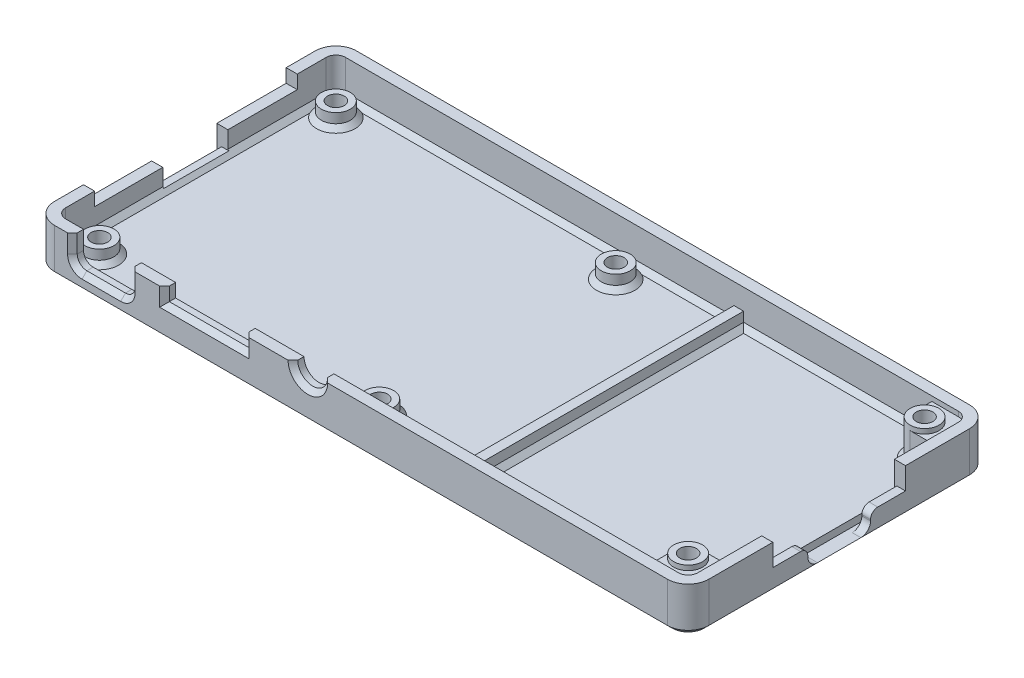
SolidWorks part; units mm, degrees
ref_plane "Front Plane" through (0, 0, 0) normal (0, 0, 1) x (1, 0, 0)
ref_plane "Top Plane" through (0, 0, 0) normal (0, 1, 0) x (1, 0, 0)
ref_plane "Right Plane" through (0, 0, 0) normal (1, 0, 0) x (0, 0, -1)
sketch "Sketch1" plane through (0, 0, 0) normal (0, 1, 0) x (1, 0, 0)
  line L0 (-71.5618, 3.106) -> (57.4382, 3.106) construction
  line L1 (-71.5618, 31.106) -> (57.4382, 31.106)
  line L2 (-71.5618, 31.106) -> (-71.5618, -24.894)
  line L3 (-71.5618, -24.894) -> (57.4382, -24.894)
  line L4 (57.4382, 31.106) -> (57.4382, -24.894)
  line L5 (-60.6618, -24.894) -> (-60.6618, -31.6828) construction
  line L6 (-68.0618, 27.606) -> (-10.0618, 27.606)
  line L7 (-68.0618, 27.606) -> (-68.0618, -21.394)
  line L8 (-68.0618, -21.394) -> (-10.0618, -21.394)
  line L9 (-10.0618, 27.606) -> (-10.0618, -21.394)
  line L10 (-39.5618, -24.894) -> (-39.5618, -31.6828) construction
  line L11 (-18.0618, -24.894) -> (-18.0618, -31.6828) construction
  line L12 (-65.4118, -26.5648) -> (-55.9118, -26.5648) construction
  line L13 (-48.0618, -26.5648) -> (-31.0618, -26.5648) construction
  line L14 (-22.0618, -26.5648) -> (-14.0618, -26.5648) construction
  line L15 (-72.5618, 9.606) -> (-72.5618, -3.394) construction
  line L16 (-71.5618, 3.106) -> (-72.5618, 3.106) construction
  dimension "D1" = 129
  dimension "D2" = 56
  dimension "D3" = 49
  dimension "D4" = 58
  dimension "D5" = 3.5
  dimension "D6" = 3.5
  dimension "D7" = 10.9
  dimension "D8" = 32
  dimension "D9" = 53.5
  dimension "D10" = 2
  dimension "D11" = 13
  dimension "D12" = 9.5
  dimension "D13" = 17
  dimension "D14" = 8
sketch "Sketch3" plane through (0, 0, 0) normal (0, 1, 0) x (1, 0, 0)
  line L4 (60.7382, 34.406) -> (-74.8618, 34.406)
  line L5 (-74.8618, 34.406) -> (-74.8618, -28.194)
  line L6 (-74.8618, -28.194) -> (60.7382, -28.194)
  line L7 (60.7382, -28.194) -> (60.7382, 34.406)
  line L8 (58.4382, 32.106) -> (-72.5618, 32.106)
  line L9 (58.4382, -25.894) -> (58.4382, 32.106)
  line L10 (-72.5618, -25.894) -> (58.4382, -25.894)
  line L11 (-72.5618, 32.106) -> (-72.5618, -25.894)
  line L12 (58.4382, 32.106) -> (-72.5618, 32.106)
  line L13 (58.4382, -25.894) -> (58.4382, 32.106)
  line L14 (-72.5618, -25.894) -> (58.4382, -25.894)
  line L15 (-72.5618, 32.106) -> (-72.5618, -25.894)
  line L16 (-7.0618, 3.106) -> (-7.0618, 34.406) construction
  line L17 (-71.5618, 3.106) -> (57.4382, 3.106) construction
  line L20 (-74.8618, 3.106) -> (52.7382, 3.106) construction
  line L25 (60.7382, -28.194) -> (60.7382, 34.406) construction
  line L26 (58.4382, -25.894) -> (58.4382, 32.106) construction
  dimension "D1" = 1
  dimension "D2" = 2.3
extrude "Boss-Extrude1" add sketch "Sketch3" along normal blind 9.3
sketch "Sketch5" plane through (0, 0, 0) normal (0, 1, 0) x (1, 0, 0)
  line L1 (-72.5618, 32.106) -> (58.4382, 32.106)
  line L2 (-72.5618, 32.106) -> (-72.5618, -25.894)
  line L3 (-72.5618, -25.894) -> (58.4382, -25.894)
  line L4 (58.4382, 32.106) -> (58.4382, -25.894)
extrude "Boss-Extrude2" add sketch "Sketch5" along normal blind 2
sketch "Sketch6" plane through (0, 2, 0) normal (0, 1, 0) x (1, 0, 0)
  circle A0 centre (-68.0618, 27.606) radius 3
  circle A1 centre (-68.0618, -21.394) radius 3
  circle A2 centre (-10.0618, -21.394) radius 3
  circle A3 centre (-10.0618, 27.606) radius 3
extrude "Boss-Extrude3" add sketch "Sketch6" along normal offset from surface (3 mm away) 4.3 up to face at (-7.0618, 9.3, -3.106)
sketch "Sketch10" plane through (0, 2, 0) normal (0, 1, 0) x (1, 0, 0)
  line L0 (58.4382, 32.106) -> (-72.5618, 32.106) construction
  line L1 (9.9382, 32.106) -> (11.9382, 32.106)
  line L2 (9.9382, 32.106) -> (9.9382, -25.894)
  line L3 (9.9382, -25.894) -> (11.9382, -25.894)
  line L4 (11.9382, 32.106) -> (11.9382, -25.894)
  line L5 (-72.5618, -25.894) -> (58.4382, -25.894) construction
  line L6 (-10.0618, 27.606) -> (-10.0618, -21.394) construction
  dimension "D1" = 2
  dimension "D2" = 20
extrude "Boss-Extrude4" add sketch "Sketch10" along normal offset from surface (3 mm away) 4.3 up to face at (-7.0618, 9.3, -3.106)
sketch "Sketch11" plane through (0, 0, 28.194) normal (0, 0, 1) x (1, 0, 0)
  line L0 (-74.8618, 9.3) -> (-74.8618, 0) construction
  line L1 (-66.8618, 9.3) -> (-54.8618, 9.3)
  line L2 (-66.8618, 9.3) -> (-66.8618, 3.5)
  line L3 (-66.8618, 3.5) -> (-54.8618, 3.5)
  line L4 (-54.8618, 9.3) -> (-54.8618, 3.5)
  line L6 (-60.8618, 9.3) -> (-60.6618, 0) construction
  line L7 (-65.4118, 0) -> (-55.9118, 0) construction
  line L9 (-47.778, 9.3) -> (-31.278, 9.3)
  line L10 (-47.778, 9.3) -> (-47.778, 6.5)
  line L11 (-47.778, 6.5) -> (-31.278, 6.5)
  line L12 (-31.278, 9.3) -> (-31.278, 6.5)
  line L14 (-39.5618, 0) -> (-39.528, 9.3) construction
  line L15 (-48.0618, 0) -> (-31.0618, 0) construction
  line L16 (-18.0618, 0) -> (-18.0618, 9.3) construction
  line L17 (-22.0618, 0) -> (-14.0618, 0) construction
  line L18 (-74.8618, 9.3) -> (60.7382, 9.3) construction
  circle A0 centre (-18.0618, 9.3) radius 3.1
  dimension "D5" = 6.2
  dimension "D1" = 0
  dimension "D2" = 12
  dimension "D3" = 0
  dimension "D4" = 16.5
  dimension "D6" = 8
  dimension "D7" = 5.8
  dimension "D8" = 2.8
extrude "Cut-Extrude1" cut sketch "Sketch11" against normal up to next
sketch "Sketch12" plane through (-74.8618, 0, 0) normal (-1, 0, 0) x (0, 0, 1)
  line L0 (-3.106, 0) -> (-3.106, 9.3) construction
  line L1 (-27.606, 0) -> (21.394, 0) construction
  line L2 (-34.406, 9.3) -> (28.194, 9.3) construction
  line L3 (-24.106, 6.5) -> (17.894, 6.5)
  line L4 (-9.7329, 6.5) -> (3.7671, 6.5)
  line L5 (-9.7329, 6.5) -> (-9.7329, 2.8)
  line L6 (-9.7329, 2.8) -> (3.7671, 2.8)
  line L7 (3.7671, 6.5) -> (3.7671, 2.8)
  line L8 (-24.106, 9.3) -> (17.894, 9.3)
  line L9 (-24.106, 9.3) -> (-24.106, 6.5)
  line L11 (17.894, 9.3) -> (17.894, 6.5)
  line L12 (-9.7329, 4.65) -> (3.7671, 4.65) construction
  point P17 (-3.106, 6.5)
  dimension "D1" = 13.5
  dimension "D2" = 2.8
  dimension "D3" = 3.7
  dimension "D4" = 6.5
extrude "Cut-Extrude2" cut sketch "Sketch12" against normal up to next contours L9 L3 L11 L8 | L7 L6 L5 L4
fillet "Fillet6" radius 2 1 edges at (58.4382, 5.65, -32.106)
fillet "Fillet8" radius 2 2 edges at (-72.5618, 5.65, 25.894) (-72.5618, 5.65, -32.106)
chamfer "Chamfer1" distance 1 angle 45 4 edges at (-68.0618, 2, 24.394) (-10.0618, 2, 24.394) (-10.0618, 2, -24.606) (-68.0618, 2, -24.606)
sketch "Sketch24" plane through (0, 2, 0) normal (0, 1, 0) x (1, 0, 0)
  line L0 (11.9382, 3.106) -> (61.5789, 3.106) construction
  line L1 (11.9382, -25.894) -> (11.9382, 32.106) construction
  line L2 (53.9382, -18.394) -> (58.4382, -18.394)
  line L3 (58.4382, -25.894) -> (58.4382, 30.106) construction
  line L4 (-68.0618, 27.606) -> (-10.0618, 27.606) construction
  line L5 (-68.0618, 27.606) -> (-68.0618, -21.394) construction
  line L6 (-68.0618, -21.394) -> (-10.0618, -21.394) construction
  line L7 (-10.0618, 27.606) -> (-10.0618, -21.394) construction
  line L8 (-10.0618, 27.606) -> (53.9382, 27.606) construction
  line L9 (-10.0618, 27.606) -> (-10.0618, -21.394) construction
  line L10 (-10.0618, -21.394) -> (53.9382, -21.394) construction
  line L11 (53.9382, 27.606) -> (53.9382, -21.394) construction
  line L12 (50.9382, -21.394) -> (50.9382, -25.894)
  line L13 (11.9382, -25.894) -> (58.4382, -25.894) construction
  line L14 (58.4382, -25.894) -> (58.4382, 30.106) construction
  line L15 (58.4382, -18.394) -> (58.4382, -25.894)
  line L16 (58.4382, -25.894) -> (50.9382, -25.894)
  line L17 (50.9382, 27.606) -> (50.9382, 32.106)
  line L18 (56.4382, 32.106) -> (-70.5618, 32.106) construction
  line L19 (53.9382, 24.606) -> (58.4382, 24.606)
  line L20 (58.4382, 24.606) -> (58.4382, 32.106)
  line L21 (58.4382, 32.106) -> (50.9382, 32.106)
  arc A0 (50.9382, -21.394) -> (53.9382, -18.394) centre (53.9382, -21.394) cw
  arc A1 (50.9382, 27.606) -> (53.9382, 24.606) centre (53.9382, 27.606) ccw
  dimension "D2" = 4.5
extrude "Boss-Extrude7" add sketch "Sketch24" along normal up to surface (7.3 mm away) up to face at (-8.3784, 9.3, -11.175)
fillet "Fillet20" radius 4.3 4 edges at (60.7382, 4.65, 28.194) (-74.8618, 4.65, -34.406) (-74.8618, 4.65, 28.194) (60.7382, 4.65, -34.406)
chamfer "Chamfer5" distance 1 angle 45 16 edges at (-71.976, 2, 25.3082) (-71.976, 2, -31.5202) (-30.3118, 2, 25.894) (-30.3118, 2, -32.106) (9.9382, 2, -3.106) (11.9382, 2, -3.106) (31.4382, 2, -32.106) (31.4382, 2, 25.894) (51.8169, 2, 19.2727) (58.4382, 2, -3.106) (51.8169, 2, -25.4847) (-72.5618, 2, -3.106) (50.9382, 2, -29.856) (56.1882, 2, -24.606) (56.1882, 2, 18.394) (50.9382, 2, 23.644)
hole_wizard "CSK for #4 Flat Head Socket Cap Screw1" positions "Sketch28" profile "Sketch27" countersink size "#4" standard "ANSI Inch"
sketch "Sketch28" plane through (0, 0, 0) normal (0, -1, 0) x (-1, 0, 0)
  point P0 (68.0618, 27.606)
  point P4 (68.0618, -21.394)
  point P8 (-53.9382, 27.606)
  point P12 (-53.9382, -21.394)
  point P15 (10.0618, -21.394)
  point P19 (10.0618, 27.606)
sketch "Sketch27" plane through (-68.0618, 0, -27.606) normal (1, 0, 0) x (0, 0, -1)
  line L0 (0, 0) -> (0, 15.0378)
  line L1 (0, 15.0378) -> (1.7272, 14)
  line L2 (1.7272, 14) -> (1.7272, 1.8805)
  line L3 (1.7272, 1.8805) -> (3.3619, 0)
  line L5 (3.3619, 0) -> (0, 0)
  line L6 (-1.7272, 1.8805) -> (-3.3619, 0) construction
  line L10 (0, 15.0378) -> (-1.7272, 14) construction
  line L11 (0, -6.35) -> (0, 107.95) construction
  dimension "Hole Dia." = 3.4544
  dimension "Hole Depth" = 14
  dimension "Near C'Sink Dia." = 6.7238
  dimension "Near C'Sink Angle" = 82
  dimension "Drill Angle" = 118
chamfer "Chamfer7" distance 1 angle 45 8 edges at (-74.8618, 0, -3.106) (-73.6023, 0, 26.9346) (-73.6023, 0, -33.1466) (-7.0618, 0, 28.194) (-7.0618, 0, -34.406) (59.4788, 0, 26.9346) (59.4788, 0, -33.1466) (60.7382, 0, -3.106)
chamfer "Chamfer8" distance 1 angle 45 1 edges at (-74.8618, 2.8, -2.9829)
sketch "Sketch29" plane through (0, 9.3, 0) normal (0, 1, 0) x (1, 0, 0)
  line L0 (53.9382, 24.606) -> (58.4382, 24.606)
  line L1 (58.4382, 24.606) -> (58.4382, 30.106)
  line L2 (56.4382, 32.106) -> (50.9382, 32.106)
  line L3 (50.9382, 32.106) -> (50.9382, 27.606)
  line L4 (53.9382, -18.394) -> (58.4382, -18.394)
  line L5 (58.4382, -18.394) -> (58.4382, -23.894)
  line L6 (56.4382, -25.894) -> (50.9382, -25.894)
  line L7 (50.9382, -25.894) -> (50.9382, -21.394)
  arc A0 (53.9382, 24.606) -> (50.9382, 27.606) centre (53.9382, 27.606) ccw
  arc A1 (56.4382, 32.106) -> (58.4382, 30.106) centre (56.4382, 30.106) cw
  arc A2 (50.9382, -21.394) -> (53.9382, -18.394) centre (53.9382, -21.394) ccw
  arc A3 (56.4382, -25.894) -> (58.4382, -23.894) centre (56.4382, -23.894) ccw
extrude "Cut-Extrude3" cut sketch "Sketch29" against normal blind 1
fillet "Fillet21" radius 2 2 edges at (-54.8618, 3.5, 27.044) (-66.8618, 3.5, 27.044)
chamfer "Chamfer9" distance 1 angle 45 9 edges at (-18.0618, 6.2, 28.194) (-31.278, 7.9, 28.194) (-39.528, 6.5, 28.194) (-47.778, 7.9, 28.194) (-54.8618, 7.4, 28.194) (-55.4476, 4.0858, 28.194) (-60.8618, 3.5, 28.194) (-66.276, 4.0858, 28.194) (-66.8618, 7.4, 28.194)
sketch "Sketch30" plane through (58.4382, 0, 0) normal (-1, 0, 0) x (0, 0, 1)
  line L1 (-16.856, 28.5) -> (10.644, 28.5)
  line L2 (-16.856, 28.5) -> (-16.856, 1)
  line L3 (-16.856, 1) -> (10.644, 1)
  line L4 (10.644, 28.5) -> (10.644, 1)
  dimension "D1" = 27.5
  dimension "D2" = 27.5
extrude "Cut-Extrude4" cut sketch "Sketch30" against normal blind 0.5 and the other way blind 0.5
sketch "Sketch31" plane through (58.9382, 0, 0) normal (-1, 0, 0) x (0, 0, 1)
  line L0 (-16.856, 3) -> (-16.856, 9.3) construction
  line L1 (-16.856, 4.75) -> (-11.106, 4.75)
  line L2 (-16.856, 4.75) -> (-16.856, 9.3)
  line L3 (-16.856, 9.3) -> (10.644, 9.3)
  line L4 (10.644, 4.75) -> (10.644, 9.3)
  line L5 (-30.106, 1) -> (23.894, 1) construction
  line L6 (4.894, 4.75) -> (10.644, 4.75)
  line L8 (-9.606, 3.25) -> (-9.606, 3)
  line L9 (-7.606, 1) -> (1.394, 1)
  line L10 (3.394, 3.25) -> (3.394, 3)
  arc A0 (3.394, 3.25) -> (4.894, 4.75) centre (4.894, 3.25) cw
  arc A1 (-11.106, 4.75) -> (-9.606, 3.25) centre (-11.106, 3.25) cw
  arc A2 (1.394, 1) -> (3.394, 3) centre (1.394, 3) ccw
  arc A3 (-9.606, 3) -> (-7.606, 1) centre (-7.606, 3) ccw
  dimension "D3" = 1.5
  dimension "D4" = 2
  dimension "D1" = 3.75
  dimension "D2" = 13
  dimension "D5" = 7.25
extrude "Cut-Extrude5" cut sketch "Sketch31" against normal through all
